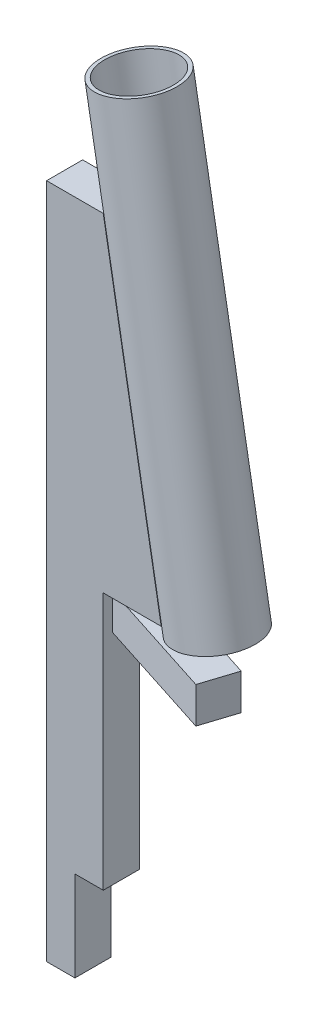
SolidWorks part; units mm, degrees
ref_plane "Front Plane" through (0, 0, 0) normal (0, 0, 1) x (1, 0, 0)
ref_plane "Top Plane" through (0, 0, 0) normal (0, 1, 0) x (1, 0, 0)
ref_plane "Right Plane" through (0, 0, 0) normal (1, 0, 0) x (0, 0, -1)
sketch "Esquisse1" plane through (0, 0, 0) normal (0, 0, 1) x (1, 0, 0)
  line L0 (0, 525.2077) -> (0, 0)
  line L1 (0, 0) -> (22, 0)
  line L2 (22, 0) -> (22, 70)
  line L3 (22, 70) -> (44, 70)
  line L4 (44, 70) -> (44, 270)
  line L5 (44, 270) -> (89, 270)
  line L6 (89, 270) -> (44, 525.2077)
  line L7 (44, 525.2077) -> (0, 525.2077)
  point P8 (-34.5857, -30.5577)
  point P9 (0, 0)
  point P11 (69.2264, 38.095)
  point P12 (0, 238.03)
  point P13 (0, 0)
  dimension "D1" = 100
  dimension "D2" = 22
  dimension "D3" = 45
  dimension "D4" = 70
  dimension "D5" = 22
  dimension "D6" = 270
extrude "Main Extrusion" add sketch "Esquisse1" along normal mid plane 28
sketch "Esquisse2" plane through (0, 270, 0) normal (0, -1, 0) x (-1, 0, 0)
  line L0 (-59.7097, -13.3264) -> (-68.2903, 13.3264) construction
  line L1 (-46.3833, -9.0361) -> (-141.5718, -39.6814)
  line L2 (-46.3833, -9.0361) -> (-54.9639, 17.6167)
  line L3 (-54.9639, 17.6167) -> (-150.1525, -13.0286)
  line L4 (-141.5718, -39.6814) -> (-150.1525, -13.0286)
  line L5 (-145.8622, -26.355) -> (-50.6736, 4.2903) construction
  line L9 (-44, -14) -> (-44, 14) construction
  point P8 (-64, 0)
  point P11 (-44, 0)
  point P12 (-128.9032, -7.6881)
  point P13 (-30.3694, 2.0228)
  point P14 (-39.818, 5.6784)
  point P15 (0, 0)
  point P16 (-30.4931, 2.1119)
  point P17 (-47.282, 1.3392)
  point P18 (-53.0881, 4.9271)
  point P19 (-53.6234, 3.0633)
  point P20 (-54.9639, 3.6167)
  dimension "D1" = 28
  dimension "D2" = 100
  dimension "D3" = 86
  dimension "D4" = 20
extrude "Boss.-Extru.2" add sketch "Esquisse2" along normal blind 28
ref_plane "Plan2" through (-43.489, 246.6386, 0) normal (0.1736, -0.9848, 0) x (0, 0, -1)
sketch "Esquisse3" plane through (-43.489, 246.6386, 0) normal (0.1736, -0.9848, 0) x (0, 0, -1)
  line L2 (-14, 134.5329) -> (14, 134.5329) construction
  line L3 (0, 82.5839) -> (0, -82.5839) construction
  circle A0 centre (0, 164.5329) radius 27
  circle A1 centre (0, 164.5329) radius 30
  point P3 (0, 0)
  point P4 (0, 64.3455)
  point P7 (-3.4508, 213.3591)
  point P8 (0, 164.5329)
  dimension "D1" = 60
  dimension "D2" = 54
extrude "Boss.-Extru.3" add sketch "Esquisse3" against normal blind 350 separate body
